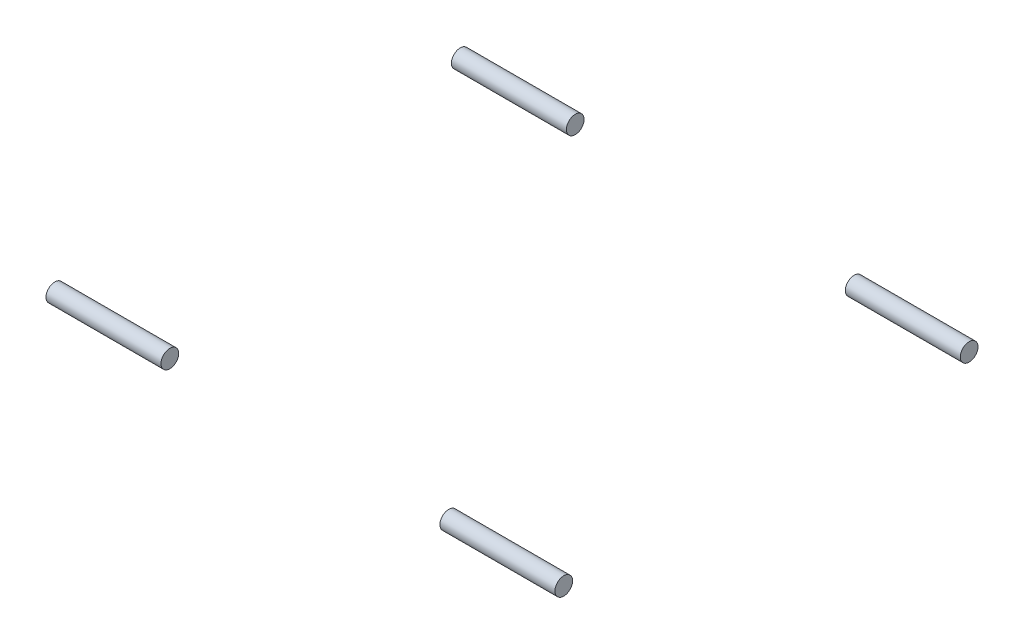
SolidWorks part; units mm, degrees
material "6061-T6 (SS)"
ref_plane "Front Plane" through (0, 0, 0) normal (0, 0, 1) x (1, 0, 0)
ref_plane "Top Plane" through (0, 0, 0) normal (0, 1, 0) x (1, 0, 0)
ref_plane "Right Plane" through (0, 0, 0) normal (1, 0, 0) x (0, 0, -1)
sketch "Sketch1" plane through (91.325, 0, 0) normal (-1, 0, 0) x (0, 0, 1)
  circle A0 centre (145.5, 0) radius 3.175
  circle A1 centre (0, 0) radius 3.175
  circle A2 centre (0, 0) radius 3.175 construction
  circle A3 centre (145.5, 0) radius 3.175 construction
extrude "Boss-Extrude1" add sketch "Sketch1" along normal up to surface (41.275 mm away)
mirror "Mirror1" about plane through (0, 0, 0) normal (1, 0, 0) of bodies 101 102
